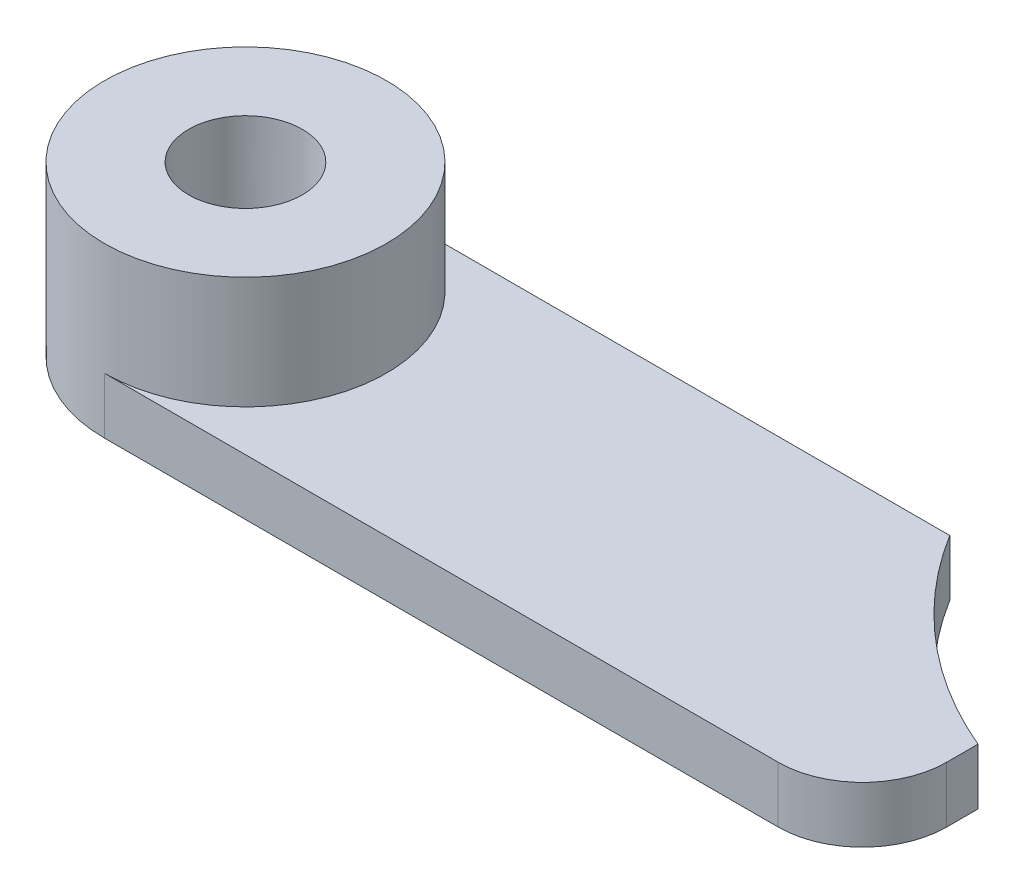
SolidWorks part; units mm, degrees
ref_plane "Front Plane" through (0, 0, 0) normal (0, 0, 1) x (1, 0, 0)
ref_plane "Top Plane" through (0, 0, 0) normal (0, 1, 0) x (1, 0, 0)
ref_plane "Right Plane" through (0, 0, 0) normal (1, 0, 0) x (0, 0, -1)
sketch "Sketch1" plane through (0, 0, 0) normal (0, 1, 0) x (1, 0, 0)
  circle A0 centre (0, 0) radius 2.025
  circle A1 centre (0, 0) radius 5.025
  dimension "D1" = 4.05
  dimension "D2" = 3
extrude "Boss-Extrude1" add sketch "Sketch1" along normal blind 6
sketch "Sketch2" plane through (0, 0, 0) normal (0, -1, 0) x (1, 0, 0)
  line L1 (0, 5.025) -> (27, 5.025)
  line L2 (0, 5.025) -> (0, -5.025)
  line L3 (0, -5.025) -> (27, -5.025)
  line L4 (27, 5.025) -> (27, -5.025)
  circle A0 centre (0, 0) radius 5.025 construction
  circle A1 centre (0, 0) radius 5.025 construction
  dimension "D1" = 27
extrude "Boss-Extrude2" add sketch "Sketch2" against normal blind 2
sketch "Sketch3" plane through (0, 2, 0) normal (0, 1, 0) x (1, 0, 0)
  circle A0 centre (32.8162, 12.9174) radius 15
  point P2 (30.143, 12.0379)
  point P3 (32.8162, 12.9174)
  dimension "D1" = 30
extrude "Cut-Extrude1" cut sketch "Sketch3" against normal blind 2
fillet "Fillet1" radius 3 1 edges at (27, 1, 5.025)
